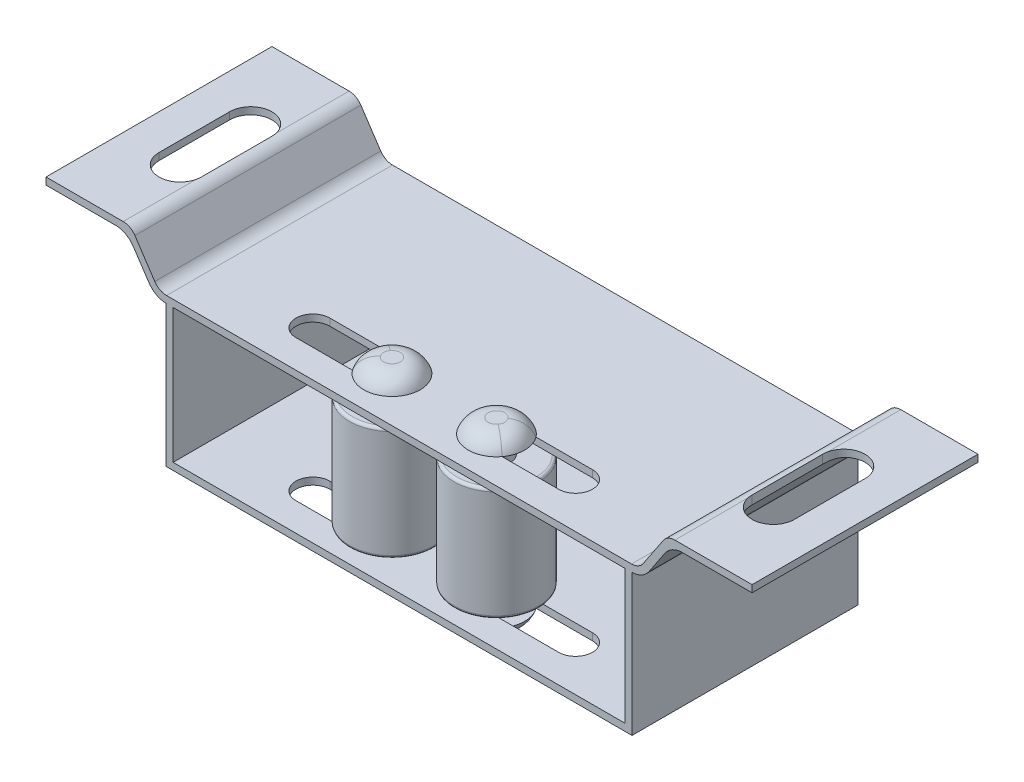
SolidWorks part; units mm, degrees
ref_plane "前视基准面" through (0, 0, 0) normal (0, 0, 1) x (1, 0, 0)
ref_plane "上视基准面" through (0, 0, 0) normal (0, 1, 0) x (1, 0, 0)
ref_plane "右视基准面" through (0, 0, 0) normal (1, 0, 0) x (0, 0, -1)
sketch "草图1" plane through (0, 0, 0) normal (0, 0, 1) x (1, 0, 0)
  line L0 (-25, 3) -> (-19, 3)
  line L1 (-19, 3) -> (-17, 0)
  line L2 (-17, 0) -> (17, 0)
  line L3 (17, 0) -> (19, 3)
  line L4 (19, 3) -> (25, 3)
  line L5 (0, 0) -> (0, 3.6056) construction
  dimension "D1" = 34
  dimension "D2" = 50
  dimension "D3" = 3
  dimension "D4" = 6
extrude "拉伸-薄壁1" add sketch "草图1" along normal mid plane 16 thin thin type one direction wall 0.5
sketch "草图2" plane through (0, -0.5, 0) normal (0, -1, 0) x (1, 0, 0)
  line L0 (-17.2676, 8) -> (17.2676, 8) construction
  line L1 (-16.5, 8) -> (16.5, 8)
  line L2 (-16.5, 8) -> (-16.5, -8)
  line L3 (-16.5, -8) -> (16.5, -8)
  line L4 (16.5, 8) -> (16.5, -8)
  line L5 (-17.2676, -8) -> (17.2676, -8) construction
  line L6 (0, 0) -> (0, 12.8251) construction
  dimension "D1" = 33
extrude "凸台-拉伸1" add sketch "草图2" along normal blind 10
shell "抽壳1" thickness 0.5 removed face at (-0.048, -0.6875, 8)
fillet "圆角1" radius 1.5 4 edges at (19.2676, 2.5, 0) (17.2676, -0.5, 0) (-19.2676, 2.5, 0) (-17.2676, -0.5, 0)
fillet "圆角2" radius 1 4 edges at (-19, 3, 0) (-17, 0, 0) (17, 0, 0) (19, 3, 0)
sketch "草图3" plane through (0, -10.5, 0) normal (0, -1, 0) x (1, 0, 0)
  line L0 (-9.3, 4.8) -> (-3.7, 4.8) construction
  line L1 (-9.3, 6) -> (-3.7, 6)
  line L2 (-9.3, 3.6) -> (-3.7, 3.6)
  line L3 (3.7, 4.8) -> (9.3, 4.8) construction
  line L4 (3.7, 6) -> (9.3, 6)
  line L5 (3.7, 3.6) -> (9.3, 3.6)
  line L6 (0, 0) -> (0, 15.721) construction
  line L7 (16.5, 8) -> (-16.5, 8) construction
  line L8 (16.5, -8) -> (16.5, 8) construction
  arc A0 (-9.3, 6) -> (-9.3, 3.6) centre (-9.3, 4.8) ccw
  arc A1 (-3.7, 3.6) -> (-3.7, 6) centre (-3.7, 4.8) ccw
  arc A2 (3.7, 6) -> (3.7, 3.6) centre (3.7, 4.8) ccw
  arc A3 (9.3, 3.6) -> (9.3, 6) centre (9.3, 4.8) ccw
  point P2 (-6.5, 4.8)
  point P7 (6.5, 4.8)
  dimension "D3" = 8
  dimension "D4" = 6
  dimension "D1" = 2.4
  dimension "D2" = 2
extrude "切除-拉伸1" cut sketch "草图3" against normal through all
ref_plane "基准面1" through (0, -5.25, 0) normal (0, -1, 0) x (1, 0, 0)
sketch "草图4" plane through (0, -5.25, 0) normal (0, -1, 0) x (1, 0, 0)
  circle A0 centre (3.7, 4.8) radius 1
  circle A1 centre (-3.7, 4.8) radius 1
  dimension "D1" = 2
extrude "凸台-拉伸2" add sketch "草图4" along normal mid plane 10.5 separate body
sketch "草图5" plane through (0, -10.5, 0) normal (0, -1, 0) x (1, 0, 0)
  circle A0 centre (3.7, 4.8) radius 2
  circle A1 centre (-3.7, 4.8) radius 2
  dimension "D1" = 4
extrude "凸台-拉伸3" add sketch "草图5" along normal blind 1
fillet "圆角3" radius 1.5 2 edges at (3.7, -11.5, 2.8) (-3.7, -11.5, 2.8)
sketch "草图6" plane through (0, 0, 0) normal (0, 1, 0) x (1, 0, 0)
  circle A0 centre (3.7, -4.8) radius 2
  circle A1 centre (-3.7, -4.8) radius 2
  dimension "D1" = 4
extrude "凸台-拉伸4" add sketch "草图6" along normal blind 1
fillet "圆角4" radius 1.5 2 edges at (-3.7, 1, 6.8) (3.7, 1, 6.8)
sketch "草图7" plane through (0, -5.25, 0) normal (0, -1, 0) x (1, 0, 0)
  circle A0 centre (3.7, 4.8) radius 3
  circle A1 centre (-3.7, 4.8) radius 3
  dimension "D1" = 6
extrude "凸台-拉伸5" add sketch "草图7" along normal mid plane 8
sketch "草图8" plane through (0, 2.5, 0) normal (0, -1, 0) x (1, 0, 0)
  line L0 (-21, 2.5) -> (-21, -2.5) construction
  line L1 (-19.5, 2.5) -> (-19.5, -2.5)
  line L2 (-22.5, 2.5) -> (-22.5, -2.5)
  line L3 (21, 2.5) -> (21, -2.5) construction
  line L4 (22.5, 2.5) -> (22.5, -2.5)
  line L5 (19.5, 2.5) -> (19.5, -2.5)
  line L6 (0, 0) -> (0, 19.883) construction
  line L7 (25, 8) -> (25, -8) construction
  arc A0 (-19.5, 2.5) -> (-22.5, 2.5) centre (-21, 2.5) ccw
  arc A1 (-22.5, -2.5) -> (-19.5, -2.5) centre (-21, -2.5) ccw
  arc A2 (22.5, 2.5) -> (19.5, 2.5) centre (21, 2.5) ccw
  arc A3 (19.5, -2.5) -> (22.5, -2.5) centre (21, -2.5) ccw
  point P2 (-21, 0)
  point P7 (21, 0)
  point P19 (25, 0)
  dimension "D3" = 8
  dimension "D1" = 3
  dimension "D2" = 42
extrude "切除-拉伸2" cut sketch "草图8" against normal mid plane 8
fillet "圆角5" radius 0.2 4 edges at (3.7, -1.25, 1.8) (3.7, -9.25, 1.8) (-3.7, -1.25, 1.8) (-3.7, -9.25, 1.8)
